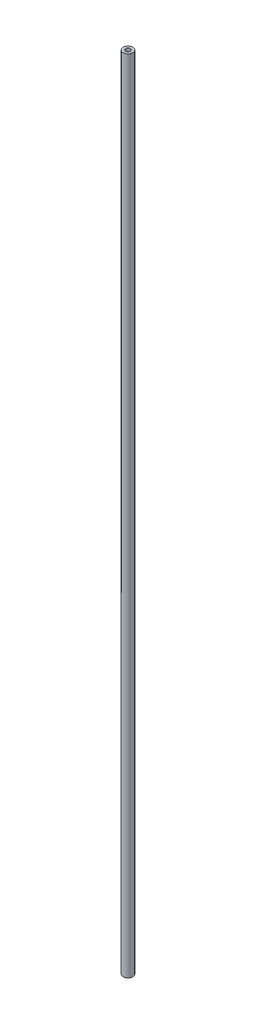
SolidWorks part; units mm, degrees
ref_plane "Front Plane" through (0, 0, 0) normal (0, 0, 1) x (1, 0, 0)
ref_plane "Top Plane" through (0, 0, 0) normal (0, 1, 0) x (1, 0, 0)
ref_plane "Right Plane" through (0, 0, 0) normal (1, 0, 0) x (0, 0, -1)
sketch "Sketch1" plane through (0, 0, 0) normal (0, 1, 0) x (1, 0, 0)
  circle A0 centre (0, 0) radius 3
  circle A1 centre (0, 0) radius 1.5
  dimension "D1" = 3
  dimension "D2" = 6
extrude "Boss-Extrude1" add sketch "Sketch1" along normal blind 500
equation "\"carbon_fiber_tube_diam\"= 1in"
equation "\"clip_tube_diam\"= 6mm"
equation "\"middle_tube_len\"= 500mm"
equation "\"D1@Boss-Extrude1\"=\"middle_tube_len\""
